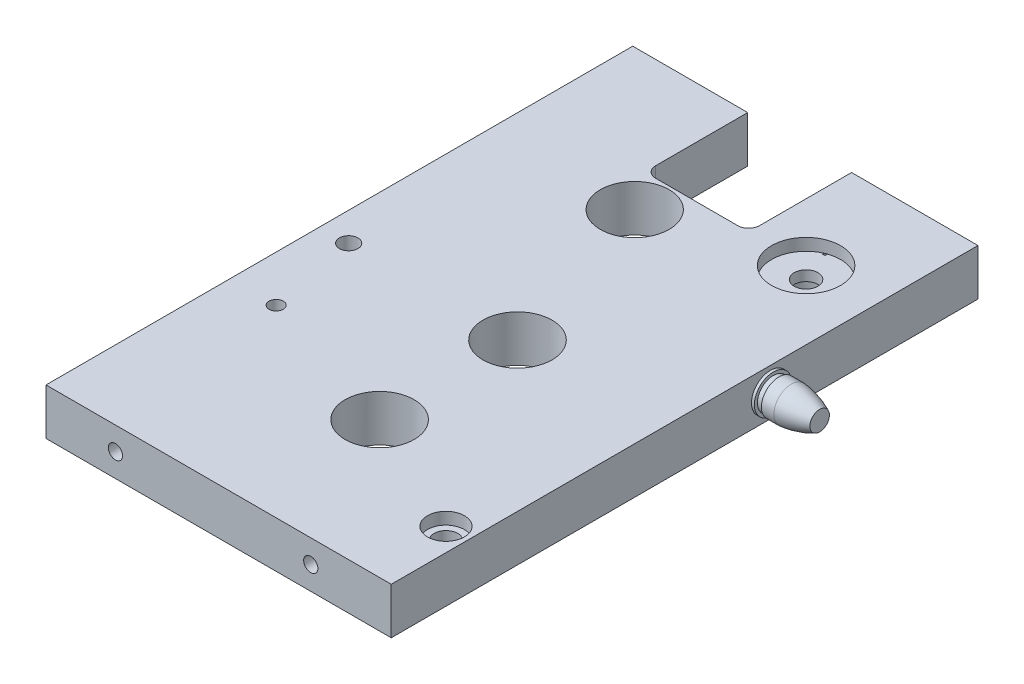
SolidWorks part; units mm, degrees
material "1060 Alloy"
ref_plane "Front Plane" through (0, 0, 0) normal (0, 0, 1) x (1, 0, 0)
ref_plane "Top Plane" through (0, 0, 0) normal (0, 1, 0) x (1, 0, 0)
ref_plane "Right Plane" through (0, 0, 0) normal (1, 0, 0) x (0, 0, -1)
sketch "Sketch1" plane through (0, 0, 0) normal (0, 0, 1) x (1, 0, 0)
  line L0 (-233.4699, -616.5) -> (-342.6239, -616.5) construction
  line L1 (-234.625, -610.1) -> (-329.875, -610.1)
  line L2 (-234.625, -610.1) -> (-234.625, -622.9)
  line L3 (-234.625, -622.9) -> (-329.875, -622.9)
  line L4 (-329.875, -610.1) -> (-329.875, -622.9)
  line L5 (-282.25, -610.1) -> (-282.25, -622.9) construction
  circle A0 centre (-307.5, -616.5) radius 3.1 construction
  circle A3 centre (-257, -616.5) radius 3.1 construction
  circle A4 centre (-244.2, -616.5) radius 2.395
  circle A5 centre (-257, -616.5) radius 3.1
  circle A6 centre (-307.5, -616.5) radius 3.1
  circle A7 centre (-320.5, -616.5) radius 2.395
  circle A10 centre (-320.5, -616.5) radius 3.425 construction
  circle A11 centre (-244.2, -616.5) radius 3.425 construction
  dimension "D3" = 4.79
  dimension "D1" = 12.8
  dimension "D2" = 95.25
extrude "Boss-Extrude1" add sketch "Sketch1" along normal blind 161.88 contours L2 L3 L4 L1
extrude "Cut-Extrude1" cut sketch "Sketch1<3>" along normal blind 20.2 contours A6 | A5 region at (-257, -616.5, 0) region at (-307.5, -616.5, 0)
sketch "Sketch1<3>" plane through (0, 0, 0) normal (0, 0, 1) x (1, 0, 0) same geometry as "Sketch1"
extrude "Cut-Extrude2" cut sketch "Sketch1<4>" along normal blind 21.5 contours A4 | A7 region at (-244.2, -616.5, 0) region at (-320.5, -616.5, 0)
sketch "Sketch1<4>" plane through (0, 0, 0) normal (0, 0, 1) x (1, 0, 0) same geometry as "Sketch1"
sketch "Sketch2" plane through (0, -610.1, 0) normal (0, 1, 0) x (1, 0, 0)
  line L0 (-234.625, 0) -> (-329.875, 0) construction
  line L1 (-269.505, 0) -> (-298.155, 0)
  line L2 (-269.505, 0) -> (-269.505, -25.4)
  line L3 (-272.505, -28.4) -> (-295.155, -28.4)
  line L4 (-298.155, 0) -> (-298.155, -25.4)
  line L5 (-272.505, -28.4) -> (-269.505, -28.4) construction
  line L6 (-269.505, -28.4) -> (-269.505, -25.4) construction
  line L7 (-295.155, -28.4) -> (-298.155, -28.4) construction
  line L8 (-298.155, -28.4) -> (-298.155, -25.4) construction
  line L9 (-275.57, -133.66) -> (-275.57, -161.88) construction
  line L10 (-234.625, -161.88) -> (-234.625, 0) construction
  line L11 (-329.875, -161.88) -> (-329.875, 0) construction
  line L12 (-234.625, -161.88) -> (-329.875, -161.88) construction
  line L13 (-266.045, -124.135) -> (-234.625, -124.135) construction
  line L14 (-266.045, -86.105) -> (-234.625, -86.105) construction
  line L15 (-275.57, -95.63) -> (-275.57, -161.88) construction
  circle A0 centre (-275.57, -124.135) radius 9.525
  circle A1 centre (-275.57, -86.105) radius 9.525
  arc A2 (-298.155, -25.4) -> (-295.155, -28.4) centre (-295.155, -25.4) ccw
  arc A3 (-272.505, -28.4) -> (-269.505, -25.4) centre (-272.505, -25.4) ccw
  dimension "D1" = 3
  dimension "D5" = 19.05
  dimension "D2" = 34.88
  dimension "D3" = 31.72
  dimension "D4" = 28.4
  dimension "D6" = 28.22
  dimension "D7" = 31.42
  dimension "D8" = 66.25
  dimension "D9" = 31.42
extrude "Cut-Extrude3" cut sketch "Sketch2" against normal up to next
sketch "Sketch3" plane through (0, -610.1, 0) normal (0, 1, 0) x (-1, 0, 0)
  line L0 (244.025, 28.505) -> (234.625, 28.505) construction
  line L1 (234.625, 161.88) -> (234.625, 0) construction
  line L2 (235.835, 140.49) -> (234.625, 140.49) construction
  line L3 (240.925, 145.58) -> (240.925, 161.88) construction
  line L4 (234.625, 161.88) -> (329.875, 161.88) construction
  line L5 (253.55, 38.03) -> (253.55, 161.88) construction
  line L6 (317.175, 111.08) -> (329.875, 111.08) construction
  line L7 (329.875, 161.88) -> (329.875, 0) construction
  line L8 (321.975, 86.28) -> (329.875, 86.28) construction
  line L9 (317.175, 111.08) -> (317.175, 161.88) construction
  line L10 (321.975, 86.28) -> (321.975, 161.88) construction
  circle A0 centre (240.925, 140.49) radius 3.265
  circle A1 centre (253.55, 28.505) radius 3.265
  circle A2 centre (240.925, 140.49) radius 5.09 construction
  circle A3 centre (253.55, 28.505) radius 9.525 construction
  circle A4 centre (317.175, 111.08) radius 1.96
  circle A5 centre (321.975, 86.28) radius 2.56
  dimension "D1" = 3.92
  dimension "D2" = 6.53
  dimension "D3" = 10.18
  dimension "D4" = 19.05
  dimension "D9" = 5.12
  dimension "D5" = 1.21
  dimension "D6" = 9.4
  dimension "D7" = 123.85
  dimension "D8" = 16.3
  dimension "D10" = 75.6
  dimension "D11" = 7.9
  dimension "D12" = 50.8
  dimension "D13" = 12.7
extrude "Cut-Extrude4" cut sketch "Sketch3" against normal up to next
sketch "Sketch4" plane through (0, -610.1, 0) normal (0, 1, 0) x (-1, 0, 0)
  circle A0 centre (253.55, 28.505) radius 9.525
  circle A1 centre (240.925, 140.49) radius 5.09
  circle A2 centre (253.55, 28.505) radius 9.525 construction
  circle A4 centre (240.925, 140.49) radius 5.09 construction
extrude "Cut-Extrude5" cut sketch "Sketch4" against normal blind 3.32
sketch "Sketch5" plane through (0, -622.9, 0) normal (0, -1, 0) x (1, 0, 0)
  circle A0 centre (-240.925, 140.49) radius 5.31
  circle A1 centre (-253.55, 28.505) radius 5.31
  circle A2 centre (-240.925, 140.49) radius 3.265 construction
  circle A3 centre (-253.55, 28.505) radius 3.265 construction
  dimension "D1" = 10.62
extrude "Cut-Extrude6" cut sketch "Sketch5" against normal blind 6.65
sketch "Sketch6" plane through (0, 0, 161.88) normal (0, 0, 1) x (1, 0, 0)
  circle A0 centre (-310.715, -616.48) radius 1.965
  circle A1 centre (-256.825, -616.48) radius 1.965
  circle A3 centre (-256.825, -616.48) radius 2.795 construction
  circle A4 centre (-310.715, -616.48) radius 2.795 construction
  dimension "D3" = 3.93
extrude "Cut-Extrude7" cut sketch "Sketch6" against normal blind 17.25
sketch "Sketch7" plane through (-329.875, 0, 0) normal (-1, 0, 0) x (0, 0, 1)
  line L0 (161.88, -616.5) -> (142.28, -616.5) construction
  line L1 (161.88, -610.1) -> (161.88, -622.9) construction
  circle A0 centre (142.28, -616.5) radius 1.97
  dimension "D1" = 3.94
  dimension "D2" = 19.6
extrude "Cut-Extrude8" cut sketch "Sketch7" against normal blind 15.87
ref_plane "Plane1" through (0, -616.5, 0) normal (0, 1, 0) x (-1, 0, 0)
sketch "Sketch8" plane through (0, -616.5, 0) normal (0, 1, 0) x (-1, 0, 0)
  line L0 (234.625, 57.29) -> (221.025, 57.29)
  line L1 (234.625, 57.29) -> (234.625, 52.09)
  line L2 (234.625, 161.88) -> (234.625, 0) construction
  line L3 (234.625, 57.29) -> (259.3185, 57.29) construction
  line L4 (234.625, 52.09) -> (233.835, 52.09)
  line L5 (233.835, 52.09) -> (233.835, 52.925)
  line L6 (233.835, 52.925) -> (232.295, 52.925)
  line L7 (232.295, 52.925) -> (232.2758, 52.475)
  line L8 (232.2758, 52.475) -> (228.8458, 52.475)
  line L9 (221.025, 57.29) -> (221.025, 54.59)
  line L10 (228.8458, 52.475) -> (228.8458, 75.3879) construction
  line L11 (228.8458, 75.3879) -> (230.8458, 75.3879) construction
  arc A0 (221.025, 54.59) -> (228.8458, 52.475) centre (230.8458, 75.3879) ccw
  dimension "D9" = 23
  dimension "D1" = 10.4
  dimension "D2" = 8.73
  dimension "D3" = 9.63
  dimension "D4" = 5.4
  dimension "D5" = 13.6
  dimension "D6" = 0.79
  dimension "D7" = 1.54
  dimension "D8" = 3.43
  dimension "D10" = 57.29
  dimension "D11" = 2
revolve "Revolve1" add sketch "Sketch8" angle 360 about L3
sketch "Sketch9" plane through (0, -622.9, 0) normal (0, -1, 0) x (1, 0, 0)
  circle A0 centre (-290.57, 38.77) radius 9.5
  circle A1 centre (-290.57, 38.77) radius 9.5 construction
extrude "Cut-Extrude9" cut sketch "Sketch9" against normal through all
